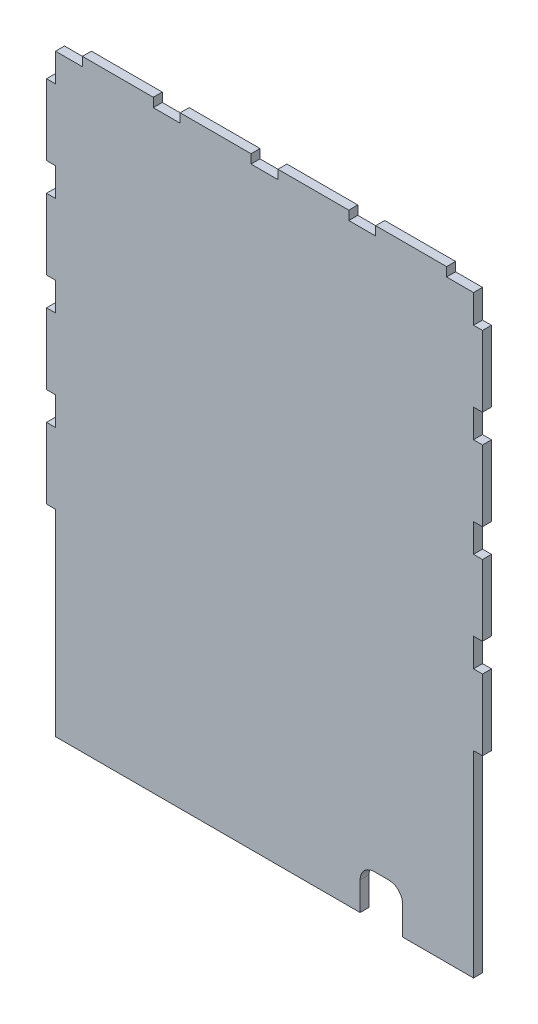
SolidWorks part; units mm, degrees
material "Beech"
ref_plane "Front Plane" through (0, 0, 0) normal (0, 0, 1) x (1, 0, 0)
ref_plane "Top Plane" through (0, 0, 0) normal (0, 1, 0) x (1, 0, 0)
ref_plane "Right Plane" through (0, 0, 0) normal (1, 0, 0) x (0, 0, -1)
sketch "Sketch2" plane through (0, 0, 0) normal (0, 0, 1) x (1, 0, 0)
  line L1 (0, 0) -> (19, 0)
  line L2 (0, 0) -> (0, -20)
  line L3 (0, -418.97) -> (295, -418.97)
  line L4 (295, 0) -> (295, -20)
  line L6 (19, 0) -> (19, 6.35)
  line L7 (19, 6.35) -> (69, 6.35)
  line L8 (69, 0) -> (69, 6.35)
  line L9 (88, 0) -> (88, 6.35)
  line L10 (88, 6.35) -> (138, 6.35)
  line L11 (138, 0) -> (138, 6.35)
  line L13 (157, 0) -> (157, 6.35)
  line L14 (157, 6.35) -> (207, 6.35)
  line L15 (207, 0) -> (207, 6.35)
  line L17 (226, 0) -> (226, 6.35)
  line L18 (226, 6.35) -> (276, 6.35)
  line L19 (276, 0) -> (276, 6.35)
  line L20 (69, 0) -> (88, 0)
  line L21 (138, 0) -> (157, 0)
  line L22 (207, 0) -> (226, 0)
  line L23 (276, 0) -> (295, 0)
  line L24 (0, -90) -> (-6.35, -90)
  line L25 (0, -20) -> (-6.35, -20)
  line L27 (0, -70) -> (-6.35, -70)
  line L28 (-6.35, -20) -> (-6.35, -70)
  line L30 (0, -140) -> (-6.35, -140)
  line L31 (-6.35, -90) -> (-6.35, -140)
  line L32 (0, -160) -> (-6.35, -160)
  line L34 (0, -210) -> (-6.35, -210)
  line L35 (-6.35, -160) -> (-6.35, -210)
  line L36 (0, -230) -> (-6.35, -230)
  line L38 (0, -280) -> (-6.35, -280)
  line L39 (-6.35, -230) -> (-6.35, -280)
  line L40 (295, -90) -> (301.35, -90)
  line L41 (295, -20) -> (301.35, -20)
  line L43 (295, -70) -> (301.35, -70)
  line L44 (301.35, -20) -> (301.35, -70)
  line L45 (295, -140) -> (301.35, -140)
  line L46 (301.35, -90) -> (301.35, -140)
  line L47 (295, -160) -> (301.35, -160)
  line L48 (295, -210) -> (301.35, -210)
  line L49 (301.35, -160) -> (301.35, -210)
  line L50 (295, -230) -> (301.35, -230)
  line L51 (295, -280) -> (301.35, -280)
  line L52 (301.35, -230) -> (301.35, -280)
  line L53 (0, -70) -> (0, -90)
  line L54 (0, -140) -> (0, -160)
  line L55 (0, -210) -> (0, -230)
  line L56 (0, -280) -> (0, -418.97)
  line L57 (295, -70) -> (295, -90)
  line L58 (295, -140) -> (295, -160)
  line L59 (295, -210) -> (295, -230)
  line L60 (295, -280) -> (295, -418.97)
  dimension "D1" = 295
  dimension "D2" = 418.97
  dimension "D3" = 6.35
  dimension "D4" = 50
  dimension "D5" = 19
  dimension "D7" = 19
  dimension "D8" = 6.35
  dimension "D9" = 50
  dimension "D10" = 20
  dimension "D12" = 138.97
  dimension "D13" = 6.35
  dimension "D14" = 20
  dimension "D15" = 50
  dimension "D17" = 138.97
  dimension "D6" = 4
  dimension "D11" = 4
  dimension "D16" = 4
extrude "Boss-Extrude1" add sketch "Sketch2" along normal blind 6.35
sketch "Sketch3" plane through (0, 0, 6.35) normal (0, 0, 1) x (1, 0, 0)
  line L0 (295, -418.97) -> (295, -280) construction
  line L1 (215, -418.97) -> (245, -418.97)
  line L2 (215, -418.97) -> (215, -388.97)
  line L3 (215, -388.97) -> (245, -388.97)
  line L4 (245, -418.97) -> (245, -388.97)
  line L5 (0, -418.97) -> (295, -418.97) construction
  dimension "D1" = 30
  dimension "D2" = 30
  dimension "D3" = 50
extrude "Cut-Extrude1" cut sketch "Sketch3" against normal through all
fillet "Fillet1" radius 10 2 edges at (245, -388.97, 3.175) (215, -388.97, 3.175)
